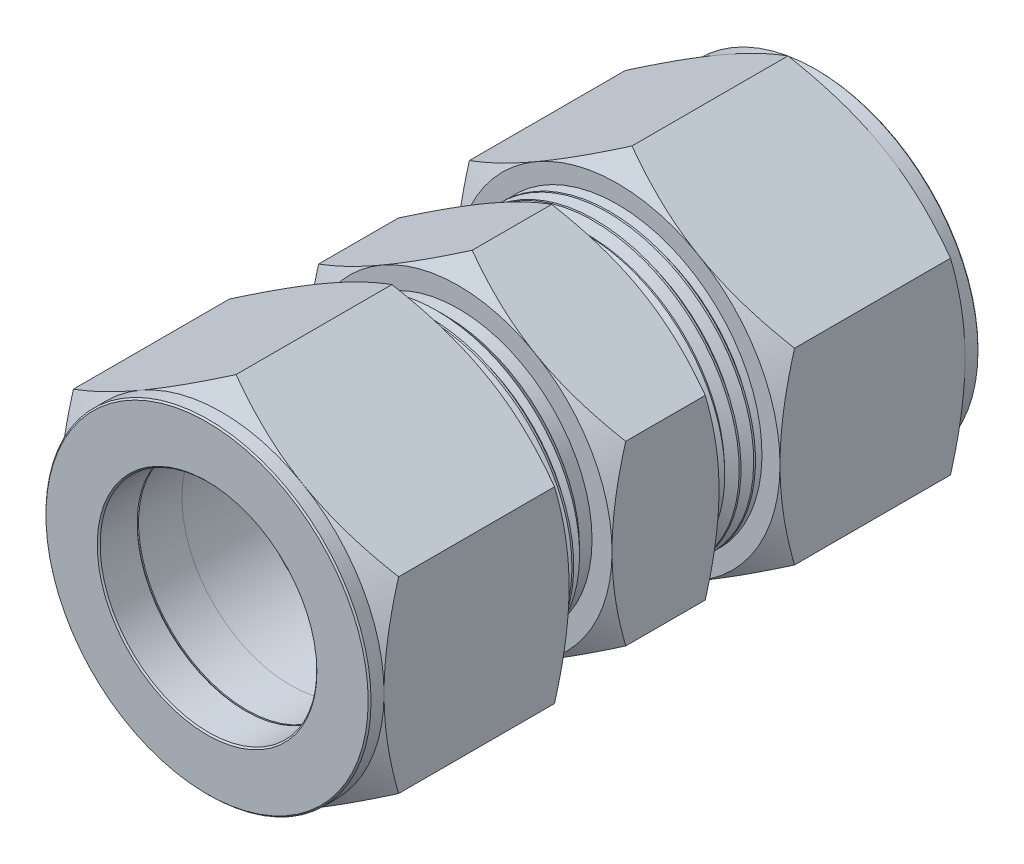
SolidWorks part; units mm, degrees
ref_plane "Front Plane" through (0, 0, 0) normal (0, 0, 1) x (1, 0, 0)
ref_plane "Top Plane" through (0, 0, 0) normal (0, 1, 0) x (1, 0, 0)
ref_plane "Right Plane" through (0, 0, 0) normal (1, 0, 0) x (0, 0, -1)
sketch "Sketch1" plane through (0, 0, 0) normal (1, 0, 0) x (0, 0, -1)
  line L0 (0, 0) -> (53.594, 0) construction
  line L1 (0, 9.525) -> (0, -9.525) construction
  line L2 (17.526, 14.2875) -> (17.526, -14.2875) construction
  line L3 (7.0104, 12.7) -> (7.0104, -12.7) construction
  line L4 (7.0104, 12.7) -> (7.0104, 11.43) construction
  line L5 (26.797, 13.4937) -> (26.797, -13.4937) construction
  line L6 (6.1976, 11.8364) -> (13.5128, 10.0584) construction
  line L7 (13.5128, 10.0584) -> (13.5128, 9.525) construction
  line L8 (13.5128, 9.525) -> (7.3152, 9.525) construction
  line L9 (7.3152, 9.525) -> (6.1976, 10.6426) construction
  line L10 (6.1976, 10.6426) -> (6.1976, 11.8364) construction
  line L11 (3.5052, 11.0363) -> (4.7752, 11.0363) construction
  line L12 (4.7752, 11.0363) -> (4.7752, 10.6426) construction
  line L13 (4.7752, 10.6426) -> (6.1976, 10.6426) construction
  line L14 (26.797, 7.9375) -> (26.797, -7.9375) construction
  line L15 (6.1976, 10.6426) -> (6.1976, 9.525) construction
  line L16 (7.3152, 9.525) -> (3.5052, 9.525) construction
  line L17 (3.5052, 9.525) -> (3.5052, 11.0363) construction
  line L18 (6.1976, 9.525) -> (7.3152, 9.525) construction
  line L19 (0, 9.525) -> (3.5052, 9.525) construction
  line L20 (3.5052, 9.525) -> (7.0104, 9.525) construction
  point P4 (1.778, 0)
  point P10 (7.0104, 0)
  point P12 (17.526, 0)
  point P15 (22.098, 0)
  point P16 (10.16, 0)
  point P17 (24.384, 0)
  point P33 (26.797, 0)
sketch "Sketch2" plane through (0, 0, 0) normal (0, 0, 1) x (1, 0, 0)
  line L0 (0, 9.525) -> (0, -9.525) construction
  line L1 (0, 16.4978) -> (-14.2875, 8.2489)
  line L2 (-14.2875, 8.2489) -> (-14.2875, -8.2489)
  line L3 (-14.2875, -8.2489) -> (0, -16.4978)
  line L4 (0, -16.4978) -> (14.2875, -8.2489)
  line L5 (14.2875, -8.2489) -> (14.2875, 8.2489)
  line L6 (14.2875, 8.2489) -> (0, 16.4978)
  line L7 (0, 16.4978) -> (0, 0) construction
  circle A0 centre (0, 0) radius 14.2875 construction
extrude "Boss-Extrude1" add sketch "Sketch2" against normal up to vertex (17.526 mm away) up to point (0, 0, -17.526)
sketch "Sketch3" plane through (0, 0, 0) normal (1, 0, 0) x (0, 0, -1)
  line L0 (0, 16.4978) -> (0, 14.2875)
  line L1 (0, 8.2489) -> (0, 16.4978) construction
  line L2 (0, 14.2875) -> (1.27, 14.2875)
  line L3 (1.27, 14.2875) -> (2.5461, 16.4978)
  line L4 (17.526, 16.4978) -> (0, 16.4978) construction
  line L5 (2.5461, 16.4978) -> (16.2499, 16.4978)
  line L6 (16.2499, 16.4978) -> (17.526, 14.2875)
  line L7 (17.526, 14.2875) -> (17.526, 16.4978)
  line L8 (17.526, 16.4978) -> (17.526, 18.7081)
  line L9 (17.526, 18.7081) -> (0, 18.7081)
  line L10 (0, 18.7081) -> (0, 16.4978)
  line L11 (0, 9.525) -> (0, 0)
  line L12 (0, 9.525) -> (0, -9.525) construction
  line L13 (0, 0) -> (17.526, 0)
  line L14 (17.526, 14.2875) -> (17.526, -14.2875) construction
  line L15 (17.526, 0) -> (17.526, 12.7)
  line L16 (17.526, 12.7) -> (7.0104, 12.7)
  line L17 (7.0104, 12.7) -> (7.0104, 11.43) construction
  line L18 (7.0104, 11.43) -> (3.5052, 11.43) construction
  line L19 (3.5052, 11.43) -> (3.5052, 9.525)
  line L20 (3.5052, 9.525) -> (0, 9.525)
  line L21 (3.5052, 11.43) -> (3.5052, 12.7) construction
  line L22 (3.5052, 12.7) -> (7.0104, 12.7) construction
  line L23 (7.0104, 12.065) -> (3.5052, 12.065)
  line L24 (3.5052, 12.065) -> (3.5052, 11.43)
  line L25 (7.0104, 12.065) -> (7.0104, 12.7)
  dimension "D1" = 30
  dimension "D2" = 1.27
revolve "Cut-Revolve1" cut sketch "Sketch3" angle 360 about L0
chamfer "Chamfer1" distance 0.127 angle 45 3 edges at (0, -9.525, 0) (0, -9.525, -3.5052) (14.2875, 0, 0)
sketch "Sketch4" plane through (0, 0, 0) normal (1, 0, 0) x (0, 0, -1)
  line L1 (26.797, 0) -> (10.16, 0)
  line L2 (26.797, 0) -> (26.797, 12.7)
  line L3 (26.797, 12.7) -> (10.16, 12.7)
  line L4 (10.16, 0) -> (10.16, 12.7)
  dimension "D1" = 16.637
revolve "Revolve1" add sketch "Sketch4" angle 360 about L1
sketch "Sketch5" plane through (0, 0, -10.16) normal (0, 0, -1) x (-1, 0, 0)
  circle A0 centre (0, 0) radius 12.7 construction
  circle A1 centre (0, 0) radius 12.7
  point P3 (0, 12.7)
curve "Helix/Spiral1" pitch 1.27 height 17.907 radius 12.7 centre (0, 0, -10.16) axis (0, 0, -1) start towards (0, 1, 0)
sketch "Sketch6" plane through (0, 0, 0) normal (1, 0, 0) x (0, 0, -1)
  line L0 (8.9694, 12.8375) -> (10.2394, 12.8375) construction
  line L1 (10.2394, 12.8375) -> (9.6044, 11.7376) construction
  line L2 (9.6044, 11.7376) -> (8.9694, 12.8375) construction
  line L3 (9.525, 11.8751) -> (9.6837, 11.8751) construction
  line L4 (9.0487, 12.7) -> (10.16, 12.7) construction
  line L5 (9.6044, 11.7376) -> (9.6044, 11.8751) construction
  line L6 (9.6044, 12.7) -> (9.6044, 12.8375) construction
  line L7 (9.525, 11.8751) -> (9.0091, 12.7687)
  line L8 (9.0091, 12.7687) -> (10.1997, 12.7687)
  line L9 (10.1997, 12.7687) -> (9.6837, 11.8751)
  line L10 (9.6837, 11.8751) -> (9.525, 11.8751)
  point P10 (9.6044, 12.7687)
  dimension "D1" = 1.27
  dimension "D2" = 0.1588
sweep "Cut-Sweep1" cut profiles "Sketch6" path "Helix/Spiral1" align with end faces yes
sketch "Sketch7" plane through (0, 0, -26.797) normal (0, 0, -1) x (-1, 0, 0)
  line L0 (0, 0) -> (0, 15.5812) construction
  line L1 (0, 15.5812) -> (-13.4938, 7.7906)
  line L2 (-13.4938, 7.7906) -> (-13.4938, -7.7906)
  line L3 (-13.4938, -7.7906) -> (0, -15.5812)
  line L4 (0, -15.5812) -> (13.4938, -7.7906)
  line L5 (13.4938, -7.7906) -> (13.4938, 7.7906)
  line L6 (13.4938, 7.7906) -> (0, 15.5812)
  circle A0 centre (0, 0) radius 13.4938 construction
extrude "Boss-Extrude2" add sketch "Sketch7" against normal up to vertex (4.699 mm away) up to point (0, 0, -22.098)
sketch "Sketch8" plane through (0, 0, 0) normal (1, 0, 0) x (0, 0, -1)
  line L0 (10.16, 12.8375) -> (10.16, 11.7376)
  line L1 (10.16, 11.7376) -> (11.2599, 12.8375)
  line L2 (11.2599, 12.8375) -> (10.16, 12.8375)
  line L3 (22.098, 12.8375) -> (19.8983, 12.8375)
  line L4 (19.8983, 12.8375) -> (20.9981, 11.7376)
  line L5 (20.9981, 11.7376) -> (22.098, 11.7376)
  line L6 (22.098, 11.7376) -> (22.098, 12.8375)
  line L7 (22.098, 13.4937) -> (23.3032, 15.5812)
  line L8 (22.098, 15.5812) -> (22.098, 7.7906) construction
  line L9 (22.098, 15.5812) -> (26.797, 15.5812) construction
  line L10 (23.3032, 15.5812) -> (26.797, 15.5812)
  line L11 (24.384, 7.9375) -> (26.797, 7.9375)
  line L13 (26.797, -7.7906) -> (26.797, 7.7906) construction
  line L14 (26.797, 15.5812) -> (26.797, 17.6687)
  line L15 (26.797, 17.6687) -> (22.098, 17.6687)
  line L16 (22.098, 17.6687) -> (22.098, 15.5812)
  line L17 (22.098, 15.5812) -> (22.098, 13.4937)
  line L18 (9.6044, 11.7376) -> (10.16, 11.7376) construction
  line L19 (10.2394, 12.8375) -> (10.16, 12.8375) construction
  line L20 (11.2599, 12.8375) -> (19.8983, 12.8375) construction
  line L21 (20.9981, 11.7376) -> (10.16, 11.7376) construction
  line L22 (10.16, 10.8733) -> (15.7074, 9.525)
  line L24 (10.16, 8.9803) -> (10.16, -11.8798) construction
  line L25 (6.1976, 11.8364) -> (13.5128, 10.0584) construction
  line L26 (26.797, 0) -> (10.16, 0)
  line L27 (10.16, 0) -> (10.16, 10.8733)
  line L28 (15.7074, 9.525) -> (24.384, 9.525)
  line L29 (24.384, 9.525) -> (24.384, 7.9375)
  line L30 (26.797, 7.9375) -> (26.797, 0)
  line L31 (24.384, 0) -> (24.384, 7.9375) construction
  line L32 (26.797, 13.4937) -> (26.797, -13.4937) construction
  dimension "D1" = 30
revolve "Cut-Revolve2" cut sketch "Sketch8" angle 360 about L0
sketch "Sketch9" plane through (0, 0, 0) normal (1, 0, 0) x (0, 0, -1)
  line L0 (6.1976, 11.8364) -> (6.1976, 10.6426)
  line L1 (6.1976, 10.6426) -> (7.3152, 9.525)
  line L2 (7.3152, 9.525) -> (13.5128, 9.525)
  line L3 (13.5128, 9.525) -> (13.5128, 10.0584)
  line L4 (13.5128, 10.0584) -> (6.1976, 11.8364)
revolve "Revolve2" add sketch "Sketch9" angle 360 about L0
sketch "Sketch10" plane through (0, 0, 0) normal (1, 0, 0) x (0, 0, -1)
  line L0 (3.5052, 11.0363) -> (4.7752, 11.0363)
  line L1 (4.7752, 11.0363) -> (4.7752, 10.6426)
  line L2 (4.7752, 10.6426) -> (6.1976, 10.6426)
  line L4 (6.1976, 10.6426) -> (7.3152, 9.525)
  line L5 (7.3152, 9.525) -> (3.5052, 9.525)
  line L6 (3.5052, 9.525) -> (3.5052, 11.0363)
revolve "Revolve3" add sketch "Sketch10" angle 360 about L0
ref_axis "Axis1" through (0, 0, -26.797) along (1, 0, 0)
pattern_circular "CirPattern1" count 2 over 360 about axis through (0, 0, -26.797) along (1, 0, 0) reverse direction yes of bodies 113 106 115 114
combine bodies "Combine1" operation type add bodies to combine 119 113
equation "\"D4@Helix/Spiral1\" = \"Straight Thread Pitch@Sketch1\""
equation "\"D3@Helix/Spiral1\" = \"D4@Helix/Spiral1\" + \"D1@Sketch4\""
equation "\"D1@Sketch6\" = \"D4@Helix/Spiral1\""
equation "\"D2@Sketch6\" = \"D1@Sketch6\" / 8"
